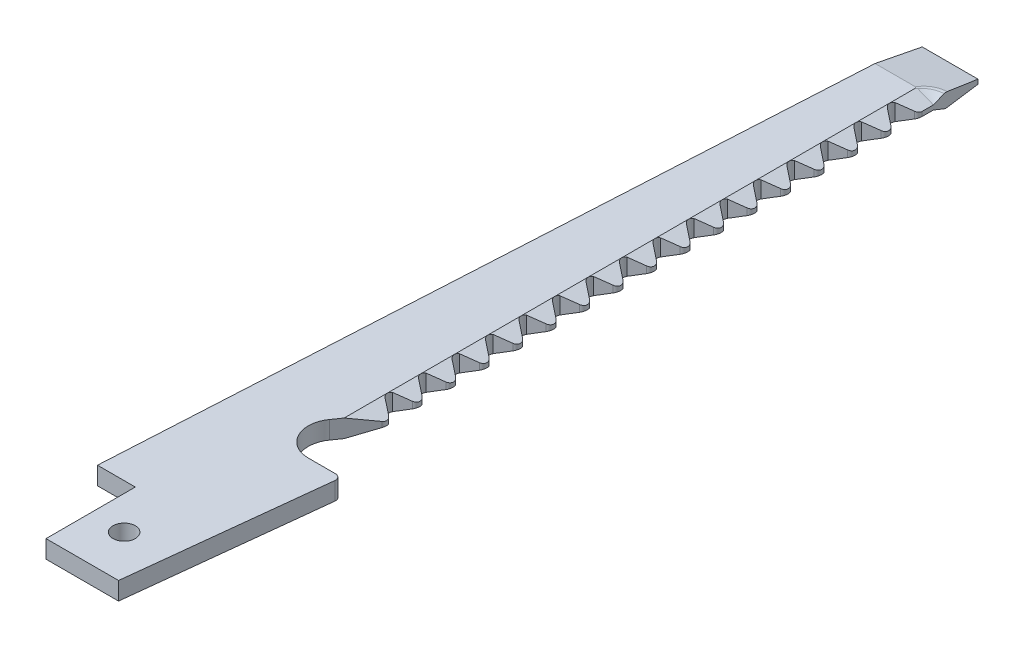
SolidWorks part; units mm, degrees
ref_plane "Płaszczyzna przednia" through (0, 0, 0) normal (0, 0, 1) x (1, 0, 0)
ref_plane "Płaszczyzna górna" through (0, 0, 0) normal (0, 1, 0) x (1, 0, 0)
ref_plane "Płaszczyzna prawa" through (0, 0, 0) normal (1, 0, 0) x (0, 0, -1)
sketch "Sketch1" plane through (0, 0, 0) normal (0, 1, 0) x (1, 0, 0)
  line L0 (0, 0) -> (0, 6)
  line L1 (0, 0) -> (12, 0) construction
  line L2 (0, 0) -> (0, 78) construction
  line L3 (0, 78) -> (12, 78) construction
  line L4 (12, 0) -> (12, 78) construction
  line L7 (9, 78) -> (9, 18)
  line L8 (9, 18) -> (12, 18)
  line L9 (12, 18) -> (10, 0)
  line L10 (10, 0) -> (0, 0)
  line L11 (9, 78) -> (4, 78)
  line L12 (4, 78) -> (0, 6)
  circle A0 centre (6.5, 4) radius 1
  point P15 (5.781, 3.8833)
  dimension "D8" = 2
  dimension "D1" = 78
  dimension "D2" = 12
  dimension "D3" = 10
  dimension "D4" = 6
  dimension "D5" = 3
  dimension "D6" = 60
  dimension "D7" = 5
  dimension "D9" = 4
  dimension "D10" = 6.5
extrude "Boss-Extrude1" add sketch "Sketch1" along normal mid plane 1.6
sketch "Sketch2" plane through (0, 0.8, 0) normal (0, 1, 0) x (1, 0, 0)
  line L0 (9, 18) -> (9, 78) construction
  line L1 (9, 73) -> (7.5, 73) construction
  line L2 (9, 73) -> (9, 70)
  line L3 (9, 70) -> (7.5, 70) construction
  line L4 (7.5, 73) -> (7.5, 70) construction
  line L5 (9, 78) -> (4, 78) construction
  line L7 (8.7504, 72.5672) -> (7.638, 71.9235)
  line L8 (7.7406, 71.1512) -> (8.7891, 70.4079)
  arc A0 (9, 73) -> (8.7504, 72.5672) centre (8.5, 73) cw
  arc A1 (7.638, 71.9235) -> (7.7406, 71.1512) centre (8, 71.5786) ccw
  arc A2 (8.7891, 70.4079) -> (9, 70) centre (8.5, 70) cw
  dimension "D4" = 0.5
  dimension "D1" = 3
  dimension "D2" = 1.5
  dimension "D3" = 5
extrude "Cut-Extrude1" cut sketch "Sketch2" against normal through all
pattern_linear "LPattern1" count 16 spacing 3 along (0, 0, 1) of "Cut-Extrude1"
sketch "Sketch3" plane through (0, 0.8, 0) normal (0, 1, 0) x (1, 0, 0)
  line L0 (9, 18) -> (9, 25) construction
  line L2 (8.9088, 24.7121) -> (6.9561, 21.9396)
  line L3 (12, 18) -> (9, 18) construction
  arc A0 (9, 25) -> (8.9088, 24.7121) centre (8.5, 25) cw
  arc A1 (6.9561, 21.9396) -> (9, 18) centre (9, 20.5) ccw
  dimension "D1" = 0.5
  dimension "D2" = 2.5
extrude "Cut-Extrude2" cut sketch "Sketch3" against normal through all and the other way through all
sketch "Sketch4" plane through (9, 0, 0) normal (1, 0, 0) x (0, 0, -1)
  line L0 (78, 0.8) -> (78, 0.2)
  line L1 (78, 0.8) -> (78, -0.8) construction
  line L2 (78, 0.2) -> (74, 0.8)
  line L3 (73, 0.8) -> (78, 0.8) construction
  line L4 (74, 0.8) -> (78, 0.8)
  line L5 (78, -0.8) -> (78, -0.2)
  line L6 (78, -0.2) -> (74, -0.8)
  line L7 (73, -0.8) -> (78, -0.8) construction
  line L8 (74, -0.8) -> (78, -0.8)
  dimension "D1" = 0.6
  dimension "D2" = 4
extrude "Cut-Extrude3" cut sketch "Sketch4" against normal through all
sketch "Sketch6" plane through (0, 0, -78) normal (0, 0, -1) x (-1, 0, 0)
  line L0 (-7.5, 0.8) -> (-9, 0.8)
  line L1 (-9, 0.8) -> (-9, 0.2) construction
  line L2 (-3.7778, 0.8) -> (-9, 0.8) construction
  line L3 (-9, 0.8) -> (-9, 0.2)
  line L4 (-9, 0.2) -> (-7.5, 0.8)
  dimension "D1" = 1.5
extrude "Cut-Extrude4" cut sketch "Sketch6" against normal blind 52.6 from offset 4 offset against normal yes
sketch "Sketch8" plane through (0, 0, -74) normal (0, 0, 1) x (1, 0, 0)
  line L3 (7.5, 0.8) -> (9, 0.2)
  line L4 (9, 0.2) -> (9, 0.8)
  line L5 (9, 0.8) -> (7.5, 0.8)
  line L6 (7.5, 0.8) -> (9, 0.2)
  line L7 (9, 0.2) -> (9, 0.8)
  line L8 (9, 0.8) -> (7.5, 0.8)
  dimension "D1" = 0
revolve "Cut-Revolve1" cut sketch "Sketch8" angle 360 about L7
mirror "Mirror1" about plane through (0, 0, 0) normal (0, 1, 0) of "Cut-Extrude4", "Cut-Revolve1"
fillet "Fillet1" radius 0.5 1 edges at (12, 0, -18)
fillet "Fillet2" radius 0.5 2 edges at (8.0955, -0.6811, -74.7927) (8.0955, 0.6811, -74.7927)
sketch "Sketch9" plane through (0, 0.8, 0) normal (0, 1, 0) x (1, 0, 0)
  line L1 (0, 0) -> (3.5, 0)
  line L2 (0, 0) -> (0, 8)
  line L3 (0, 8) -> (3.5, 8)
  line L4 (3.5, 0) -> (3.5, 8)
  dimension "D1" = 8
  dimension "D2" = 3.5
extrude "Cut-Extrude5" cut sketch "Sketch9" against normal through all
